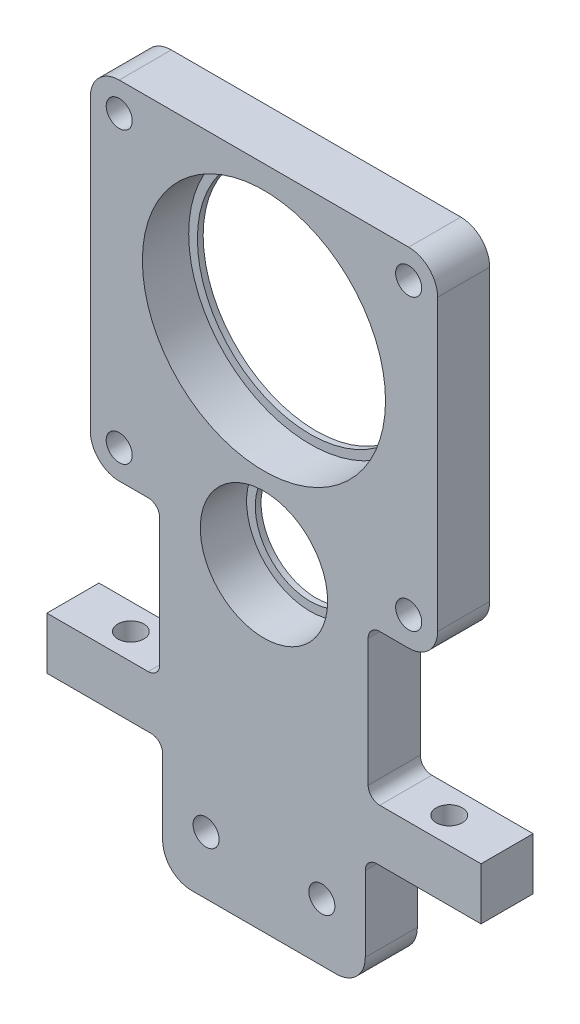
SolidWorks part; units mm, degrees
ref_plane "Plan de face" through (0, 0, 0) normal (0, 0, 1) x (1, 0, 0)
ref_plane "Plan de dessus" through (0, 0, 0) normal (0, 1, 0) x (1, 0, 0)
ref_plane "Plan de droite" through (0, 0, 0) normal (1, 0, 0) x (0, 0, -1)
sketch "Esquisse1" plane through (0, 0, 0) normal (0, 0, 1) x (1, 0, 0)
  line L1 (0, 0) -> (75, 0)
  line L2 (0, 0) -> (0, 95)
  line L3 (0, 95) -> (75, 95)
  line L4 (75, 0) -> (75, 95)
  dimension "D1" = 75
  dimension "D2" = 95
extrude "Boss.-Extru.1" add sketch "Esquisse1" along normal blind 9
sketch "Esquisse2" plane through (0, 0, 9) normal (0, 0, 1) x (1, 0, 0)
  line L0 (0, 0) -> (75, 0) construction
  line L1 (20, 0) -> (55, 0)
  line L2 (20, 0) -> (20, -20)
  line L3 (20, -20) -> (55, -20)
  line L4 (55, 0) -> (55, -20)
  line L5 (37.5, 0) -> (37.5, -20) construction
  dimension "D1" = 20
  dimension "D2" = 35
extrude "Boss.-Extru.2" add sketch "Esquisse2" against normal up to vertex (9 mm away) up to point (75, 0, 0)
sketch "Esquisse3" plane through (0, 0, 9) normal (0, 0, 1) x (1, 0, 0)
  line L0 (37.5, 70) -> (37.5, 0) construction
  line L1 (20, 0) -> (37.5, 0) construction
  line L2 (37.5, 0) -> (55, 0) construction
  line L3 (37.5, 70) -> (37.5, 95) construction
  line L4 (75, 95) -> (0, 95) construction
  circle A0 centre (37.5, 70) radius 21
  circle A1 centre (37.5, 35) radius 11
  dimension "D2" = 42
  dimension "D3" = 35
  dimension "D4" = 22
  dimension "D1" = 70
extrude "Enlèv. mat.-Extru.1" cut sketch "Esquisse3" against normal blind 8
sketch "Esquisse4" plane through (0, 0, 9) normal (0, 0, 1) x (1, 0, 0)
  circle A0 centre (37.5, 70) radius 19.5
  circle A1 centre (37.5, 70) radius 21 construction
  circle A2 centre (37.5, 35) radius 9.5
  circle A3 centre (37.5, 35) radius 11 construction
  dimension "D1" = 1.5
  dimension "D2" = 1.5
extrude "Enlèv. mat.-Extru.2" cut sketch "Esquisse4" against normal through all
sketch "Esquisse5" plane through (0, 0, 9) normal (0, 0, 1) x (1, 0, 0)
  line L0 (37.5, -20) -> (37.5, 95) construction
  line L1 (20, -20) -> (55, -20) construction
  line L2 (75, 95) -> (0, 95) construction
  line L4 (75, 9) -> (67.5, 9)
  line L5 (75, 9) -> (75, 95)
  line L6 (75, 95) -> (67.5, 95)
  line L7 (67.5, 9) -> (67.5, 95)
  line L8 (55, 0) -> (75, 0) construction
  line L9 (7.5, 9) -> (7.5, 95)
  line L10 (0, 95) -> (7.5, 95)
  line L11 (0, 9) -> (0, 95)
  line L12 (0, 9) -> (7.5, 9)
  line L13 (75, 0) -> (75, 95) construction
  point P12 (67.5, 52)
  dimension "D1" = 60
  dimension "D2" = 9
extrude "Enlèv. mat.-Extru.3" cut sketch "Esquisse5" against normal through all both and the other way through all
sketch "Esquisse8" plane through (0, 0, 9) normal (0, 0, 1) x (1, 0, 0)
  line L0 (37.5, -20) -> (37.5, -1.7723) construction
  line L1 (7.5, 9) -> (19.5, 9)
  line L2 (7.5, 9) -> (7.5, 35)
  line L3 (7.5, 35) -> (19.5, 35)
  line L4 (19.5, 9) -> (19.5, 35)
  line L5 (20, -20) -> (55, -20) construction
  line L6 (55.5, 9) -> (55.5, 35)
  line L7 (67.5, 35) -> (55.5, 35)
  line L8 (67.5, 9) -> (67.5, 35)
  line L9 (67.5, 9) -> (55.5, 9)
  dimension "D1" = 12
  dimension "D2" = 26
extrude "Enlèv. mat.-Extru.6" cut sketch "Esquisse8" against normal up to vertex (9 mm away) up to point (67.5, 9, 0)
fillet "Congé1" radius 2 6 edges at (55, 0, 4.5) (20, 0, 4.5) (55.5, 35, 4.5) (55.5, 9, 4.5) (19.5, 9, 4.5) (19.5, 35, 4.5)
fillet "Congé2" radius 5 6 edges at (55, -20, 4.5) (20, -20, 4.5) (7.5, 95, 4.5) (67.5, 95, 4.5) (67.5, 35, 4.5) (7.5, 35, 4.5)
sketch "Esquisse6" plane through (0, 0, 9) normal (0, 0, 1) x (1, 0, 0)
  line L0 (20, -10) -> (55, -10) construction
  line L1 (20, -2) -> (20, -15) construction
  line L2 (55, -15) -> (55, -2) construction
  line L3 (57, 0) -> (75, 0) construction
  line L4 (37.5, -10) -> (37.5, -20) construction
  line L5 (25, -20) -> (50, -20) construction
  line L6 (7.5, 40) -> (12.5, 40) construction
  line L7 (7.5, 90) -> (7.5, 40) construction
  line L8 (12.5, 40) -> (12.5, 90) construction
  line L9 (12.5, 90) -> (7.5, 90) construction
  line L10 (17.5, 9) -> (0, 9) construction
  line L11 (62.5, 90) -> (67.5, 90) construction
  line L12 (62.5, 40) -> (62.5, 90) construction
  line L13 (67.5, 40) -> (62.5, 40) construction
  circle A0 centre (47.5, -10) radius 2.25
  circle A1 centre (27.5, -10) radius 2.25
  circle A2 centre (12.5, 90) radius 2.25
  circle A3 centre (12.5, 40) radius 2.25
  circle A4 centre (62.5, 40) radius 2.25
  circle A5 centre (62.5, 90) radius 2.25
  dimension "D2" = 4.5
  dimension "D3" = 10
  dimension "D7" = 4.5
  dimension "D1" = 10
  dimension "D4" = 31
  dimension "D5" = 50
  dimension "D6" = 5
extrude "Enlèv. mat.-Extru.4" cut sketch "Esquisse6" against normal through all
sketch "Esquisse7" plane through (0, 9, 0) normal (0, 1, 0) x (1, 0, 0)
  line L0 (10, 0) -> (10, -9) construction
  line L1 (0, 0) -> (17.5, 0) construction
  line L2 (17.5, -9) -> (0, -9) construction
  line L3 (20, -9) -> (20, 0) construction
  line L5 (37.5, -9) -> (37.5, 0) construction
  line L6 (62.5, -9) -> (12.5, -9) construction
  line L7 (62.5, 0) -> (12.5, 0) construction
  line L8 (65, 0) -> (65, -9) construction
  circle A0 centre (10, -4.5) radius 2.25
  circle A1 centre (65, -4.5) radius 2.25
  dimension "D1" = 4.5
  dimension "D2" = 10
extrude "Enlèv. mat.-Extru.5" cut sketch "Esquisse7" against normal through all
